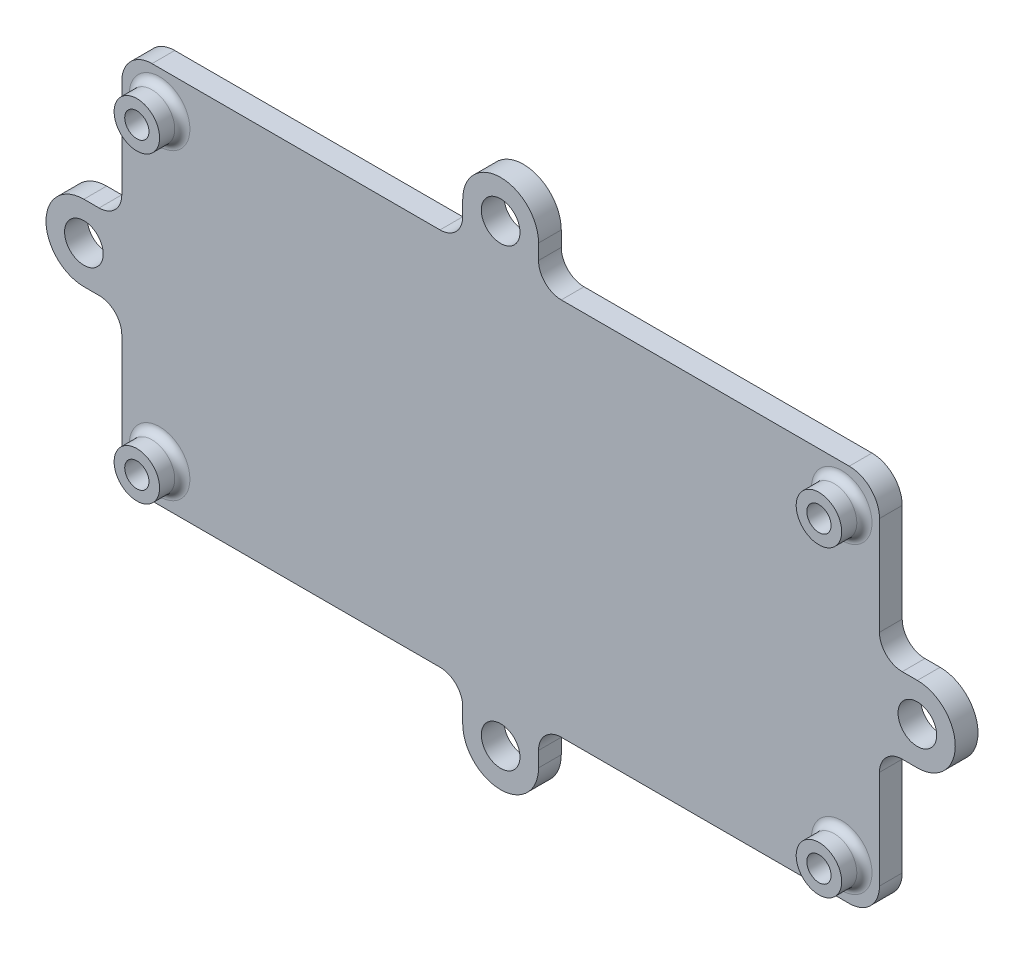
SolidWorks part; units mm, degrees
note: The reader was unsure of these and kept them because the rebuilt part matched: shared geometry of "Sketch1<3>".
ref_plane "Front Plane" through (0, 0, 0) normal (0, 0, 1) x (1, 0, 0)
ref_plane "Top Plane" through (0, 0, 0) normal (0, 1, 0) x (1, 0, 0)
ref_plane "Right Plane" through (0, 0, 0) normal (1, 0, 0) x (0, 0, -1)
sketch "Sketch1" plane through (0, 0, 0) normal (0, 0, 1) x (1, 0, 0)
  line L0 (4, 0.0127) -> (96.0002, 0.0127)
  line L1 (99.9875, 4) -> (99.9875, 46.0001)
  line L2 (96.0002, 49.9874) -> (4, 49.9874)
  line L3 (0.0127, 46.0001) -> (0.0127, 4)
  circle A0 centre (5, 45.0001) radius 1.6
  circle A1 centre (95.0002, 45.0001) radius 1.6
  circle A2 centre (95.0002, 5) radius 1.6
  circle A3 centre (5, 5) radius 1.6
  arc A4 (0.0127, 4) -> (4, 0.0127) centre (4, 4) ccw
  arc A5 (4, 49.9874) -> (0.0127, 46.0001) centre (4, 46.0001) ccw
  arc A6 (96.0002, 49.9874) -> (99.9875, 46.0001) centre (96.0002, 46.0001) cw
  arc A7 (99.9875, 4) -> (96.0002, 0.0127) centre (96.0002, 4) cw
  circle A8 centre (5, 45.0001) radius 3
  circle A9 centre (95.0002, 45.0001) radius 3
  circle A10 centre (5, 5) radius 3
  circle A11 centre (95.0002, 5) radius 3
extrude "Boss-Extrude1" add sketch "Sketch1" along normal blind 3 contours A7 L1 A6 L2 A5 L3 A4 L0 A11 A10 A9 A8
extrude "Boss-Extrude2" add sketch "Sketch1<3>" along normal blind 6 contours A8 A0 | A9 A1 | A11 A2 | A10 A3
sketch "Sketch1<3>" plane through (0, 0, 0) normal (0, 0, 1) x (1, 0, 0) same geometry as "Sketch1"
fillet "Fillet1" radius 1 4 edges at (98.0002, 5, 3) (98.0002, 45.0001, 3) (8, 45.0001, 3) (8, 5, 3)
sketch "Sketch2" plane through (0, 0, 3) normal (0, 0, 1) x (1, 0, 0)
  line L0 (0.0127, 25) -> (99.9875, 25)
  line L1 (0.0127, 46.0001) -> (0.0127, 4) construction
  line L2 (99.9875, 4) -> (99.9875, 46.0001) construction
  line L3 (50.0001, 25) -> (50.0001, 49.9874)
  line L4 (96.0002, 49.9874) -> (4, 49.9874) construction
  line L5 (50.0001, 25) -> (50.0001, 0.0127)
  line L6 (4, 0.0127) -> (96.0002, 0.0127) construction
  line L7 (50.0001, 49.9874) -> (50.0001, 54.9874)
  line L8 (99.9875, 25) -> (104.9875, 25)
  line L9 (50.0001, 0.0127) -> (50.0001, -4.9873)
  line L10 (0.0127, 25) -> (-4.9873, 25)
  line L11 (-4.9873, 30) -> (0.0127, 30)
  line L12 (-4.9873, 20) -> (0.0127, 20)
  line L13 (55.0001, -4.9873) -> (55.0001, 0.0127)
  line L14 (45.0001, -4.9873) -> (45.0001, 0.0127)
  line L15 (104.9875, 20) -> (99.9875, 20)
  line L16 (104.9875, 30) -> (99.9875, 30)
  line L17 (45.0001, 54.9874) -> (45.0001, 49.9874)
  line L18 (55.0001, 54.9874) -> (55.0001, 49.9874)
  circle A0 centre (-4.9873, 25) radius 2.55
  circle A1 centre (50.0001, 54.9874) radius 2.55
  circle A2 centre (50.0001, -4.9873) radius 2.55
  circle A3 centre (104.9875, 25) radius 2.55
  circle A4 centre (50.0001, 54.9874) radius 5
  circle A5 centre (104.9875, 25) radius 5
  circle A6 centre (50.0001, -4.9873) radius 5
  circle A7 centre (-4.9873, 25) radius 5
extrude "Boss-Extrude3" add sketch "Sketch2" against normal up to surface (3 mm away)
fillet "Fillet2" radius 3 8 edges at (0.0127, 30, 1.5) (0.0127, 20, 1.5) (45.0001, 0.0127, 1.5) (55.0001, 0.0127, 1.5) (99.9875, 20, 1.5) (99.9875, 30, 1.5) (55.0001, 49.9874, 1.5) (45.0001, 49.9874, 1.5)
